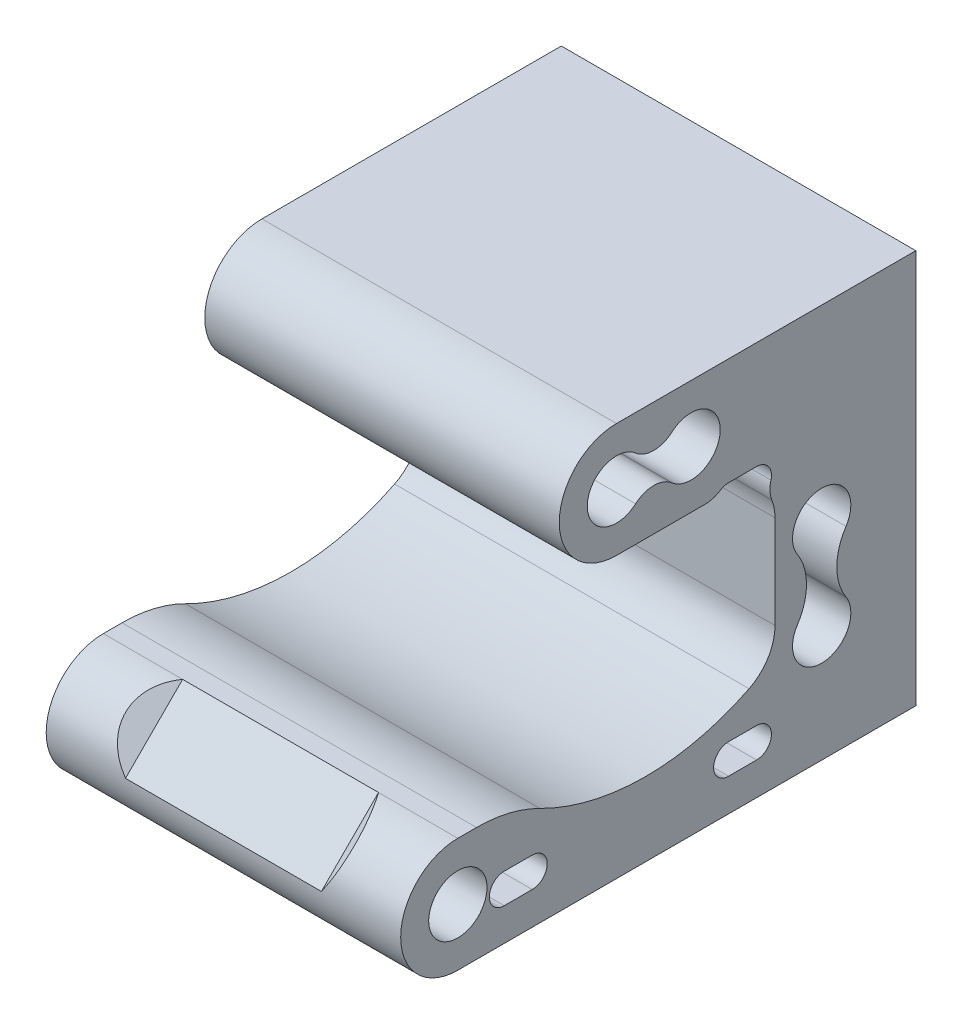
SolidWorks part; units mm, degrees
material "ABS"
ref_plane "Front Plane" through (0, 0, 0) normal (0, 0, 1) x (1, 0, 0)
ref_plane "Top Plane" through (0, 0, 0) normal (0, 1, 0) x (1, 0, 0)
ref_plane "Right Plane" through (0, 0, 0) normal (1, 0, 0) x (0, 0, -1)
ref_axis "X" through (-88.99, 0, 0) along (1, 0, 0)
ref_axis "Y" through (0, 55, 0) along (0, -1, 0)
ref_axis "Z" through (0, 0, -88.99) along (0, 0, 1)
sketch "Sketch1" plane through (0, 0, 0) normal (1, 0, 0) x (0, 0, -1)
  line L0 (-3, 19) -> (5, 19) construction
  line L1 (19, 5) -> (19, -5) construction
  line L2 (0, 0) -> (0, 19) construction
  line L3 (0, 0) -> (19, 0) construction
  line L4 (0, 0) -> (0, -11) construction
  line L5 (0, -11) -> (-20, -11) construction
  line L6 (1, 20.625) -> (1, 17.375) construction
  line L7 (20.625, 0) -> (17.375, 0) construction
  line L8 (-20, -17.125) -> (29.091, -17.125)
  line L10 (14, -2.125) -> (14, 7.875)
  line L11 (9, 12.875) -> (-3, 12.875)
  line L12 (-3, 25.125) -> (29.091, 25.125)
  line L13 (29.091, 25.125) -> (29.091, -17.125)
  line L14 (-20, -4.875) -> (-18, -4.875)
  line L15 (-26.125, -11) -> (-20, -4.875)
  circle A0 centre (-3, 19) radius 1.5 construction
  circle A1 centre (5, 19) radius 1.5 construction
  circle A2 centre (19, 5) radius 1.5 construction
  circle A3 centre (19, -5) radius 1.5 construction
  circle A4 centre (-20, -11) radius 1.5 construction
  circle A5 centre (-3, 19) radius 3.125
  circle A6 centre (5, 19) radius 3.125
  circle A7 centre (19, 5) radius 3.125
  circle A8 centre (19, -5) radius 3.125
  circle A9 centre (-20, -11) radius 3.125
  arc A10 (-0.9452, 21.3545) -> (2.9452, 21.3545) centre (1, 23.5833) ccw
  arc A11 (2.9452, 16.6455) -> (-0.9452, 16.6455) centre (1, 14.4167) ccw
  arc A12 (16.3911, 3.2798) -> (16.3911, -3.2798) centre (11.4167, 0) cw
  arc A13 (21.6089, 3.2798) -> (21.6089, -3.2798) centre (26.5833, 0) ccw
  arc A14 (-20, -4.875) -> (-20, -17.125) centre (-20, -11) ccw
  arc A15 (11.2225, -6.6039) -> (14, -2.125) centre (9, -2.125) ccw
  arc A16 (14, 7.875) -> (9, 12.875) centre (9, 7.875) ccw
  arc A17 (-3, 12.875) -> (-3, 25.125) centre (-3, 19) cw
  arc A18 (11.2225, -6.6039) -> (-11.2088, -6.5004) centre (0.1099, 15.7905) cw
  arc A19 (-11.2088, -6.5004) -> (-18, -4.875) centre (-18, -19.875) ccw
  point P16 (19, 0)
  dimension "D1" = 3
  dimension "D9" = 6.25
  dimension "D11" = 5
  dimension "D14" = 25
  dimension "D17" = 15
  dimension "D2" = 19
  dimension "D3" = 3
  dimension "D4" = 5
  dimension "D5" = 19
  dimension "D6" = 10
  dimension "D7" = 11
  dimension "D8" = 20
  dimension "D10" = 3.25
  dimension "D12" = 3
  dimension "D13" = 5
  dimension "D15" = 2
  dimension "D16" = 10
extrude "Boss-Extrude1" add sketch "Sketch1" along normal mid plane 38 contours A17 L11 A16 L10 A15 A14 L8 L13 L12 A9 A6 A11 A5 A10 A7 A13 A8 A12 | A14 region at (0, -14.8394, 23.8394) region at (0, -7.4231, 23.5769)
sketch "Sketch2" plane through (0, 0, 0) normal (1, 0, 0) x (0, 0, -1)
  line L1 (12.0208, -12.0208) -> (-12.0208, -12.0208) construction
  line L2 (12.0208, -12.0208) -> (12.0208, 12.0208) construction
  line L3 (12.0208, 12.0208) -> (-12.0208, 12.0208) construction
  line L4 (-12.0208, -12.0208) -> (-12.0208, 12.0208) construction
  line L5 (12.0208, -12.0208) -> (-12.0208, 12.0208) construction
  line L6 (12.0208, 12.0208) -> (-12.0208, -12.0208) construction
  line L7 (12.0208, 12.0208) -> (9.0208, 12.0208) construction
  line L8 (12.0208, 10.4208) -> (9.0208, 10.4208)
  line L9 (12.0208, 13.6208) -> (9.0208, 13.6208)
  line L10 (-12.0208, 12.0208) -> (-15.0208, 12.0208) construction
  line L11 (-12.0208, 10.4208) -> (-15.0208, 10.4208)
  line L12 (-12.0208, 13.6208) -> (-15.0208, 13.6208)
  line L13 (-12.0208, -12.0208) -> (-15.0208, -12.0208) construction
  line L14 (-12.0208, -13.6208) -> (-15.0208, -13.6208)
  line L15 (-12.0208, -10.4208) -> (-15.0208, -10.4208)
  line L16 (12.0208, -12.0208) -> (9.0208, -12.0208) construction
  line L17 (12.0208, -13.6208) -> (9.0208, -13.6208)
  line L18 (12.0208, -10.4208) -> (9.0208, -10.4208)
  line L19 (-12.0208, 9.0208) -> (-15.0208, 9.0208)
  line L20 (-12.0208, 15.0208) -> (-15.0208, 15.0208)
  line L21 (-12.0208, -15.0208) -> (-15.0208, -15.0208)
  line L22 (-12.0208, -9.0208) -> (-15.0208, -9.0208)
  line L23 (12.0208, -15.0208) -> (9.0208, -15.0208)
  line L24 (12.0208, -9.0208) -> (9.0208, -9.0208)
  line L25 (12.0208, 9.0208) -> (9.0208, 9.0208)
  line L26 (12.0208, 15.0208) -> (9.0208, 15.0208)
  circle A0 centre (0, 0) radius 17 construction
  arc A1 (12.0208, 10.4208) -> (12.0208, 13.6208) centre (12.0208, 12.0208) ccw
  arc A2 (9.0208, 13.6208) -> (9.0208, 10.4208) centre (9.0208, 12.0208) ccw
  arc A3 (-12.0208, 10.4208) -> (-12.0208, 13.6208) centre (-12.0208, 12.0208) ccw
  arc A4 (-15.0208, 13.6208) -> (-15.0208, 10.4208) centre (-15.0208, 12.0208) ccw
  arc A5 (-12.0208, -13.6208) -> (-12.0208, -10.4208) centre (-12.0208, -12.0208) ccw
  arc A6 (-15.0208, -10.4208) -> (-15.0208, -13.6208) centre (-15.0208, -12.0208) ccw
  arc A7 (12.0208, -13.6208) -> (12.0208, -10.4208) centre (12.0208, -12.0208) ccw
  arc A8 (9.0208, -10.4208) -> (9.0208, -13.6208) centre (9.0208, -12.0208) ccw
  arc A9 (-15.0208, 15.0208) -> (-15.0208, 9.0208) centre (-15.0208, 12.0208) ccw
  arc A10 (-12.0208, 9.0208) -> (-12.0208, 15.0208) centre (-12.0208, 12.0208) ccw
  arc A11 (-15.0208, -9.0208) -> (-15.0208, -15.0208) centre (-15.0208, -12.0208) ccw
  arc A12 (-12.0208, -15.0208) -> (-12.0208, -9.0208) centre (-12.0208, -12.0208) ccw
  arc A13 (9.0208, -9.0208) -> (9.0208, -15.0208) centre (9.0208, -12.0208) ccw
  arc A14 (12.0208, -15.0208) -> (12.0208, -9.0208) centre (12.0208, -12.0208) ccw
  arc A15 (9.0208, 15.0208) -> (9.0208, 9.0208) centre (9.0208, 12.0208) ccw
  arc A16 (12.0208, 9.0208) -> (12.0208, 15.0208) centre (12.0208, 12.0208) ccw
  point P11 (10.5208, 12.0208)
  point P20 (-13.5208, 12.0208)
  point P29 (-13.5208, -12.0208)
  point P38 (10.5208, -12.0208)
  dimension "D1" = 34
  dimension "D2" = 3
  dimension "D3" = 1.6
  dimension "D4" = 3
extrude "Cut-Extrude1" cut sketch "Sketch2" against normal through all both and the other way through all contours L12 A4 L11 A3 | L9 A2 L8 A1 | L18 A8 L17 A7 | L15 A6 L14 A5 region at (0, 12.0208, -10.5208) region at (0, 12.0208, 13.5208) region at (0, -12.0208, 13.5208) region at (0, -12.0208, -10.5208)
extrude "Cut-Extrude2" cut sketch "Sketch2<3>" along normal blind 4 from surface starting at face at (-19, -12.0208, 13.5208)
sketch "Sketch2<3>" plane through (0, 0, 0) normal (1, 0, 0) x (0, 0, -1) same geometry as "Sketch2"
fillet "Fillet2" radius 3 6 edges at (-17, 12.875, -6.145) (-17, 9.5438, -13.7133) (2, 12.875, -7.6679) (2, 10.8001, -13.0551) (-17, -13.1991, 17.7797) (-17, -9.852, 17.0935)
extrude "Cut-Extrude6" cut sketch "Sketch1<4>" against normal mid plane 25 contours L15 A14 region at (0, -7.4231, 23.5769)
sketch "Sketch1<4>" plane through (0, 0, 0) normal (1, 0, 0) x (0, 0, -1) same geometry as "Sketch1"
chamfer "Chamfer1" distance 2 angle 45 2 edges at (12.5, -7.9375, 23.0625) (-12.5, -7.9375, 23.0625)
equation "\"TOL\"= 0.25mm"
equation "\"D10@Sketch1\"=\"TOL\"+3"
equation "\"D9@Sketch1\"=\"TOL\"+6"
